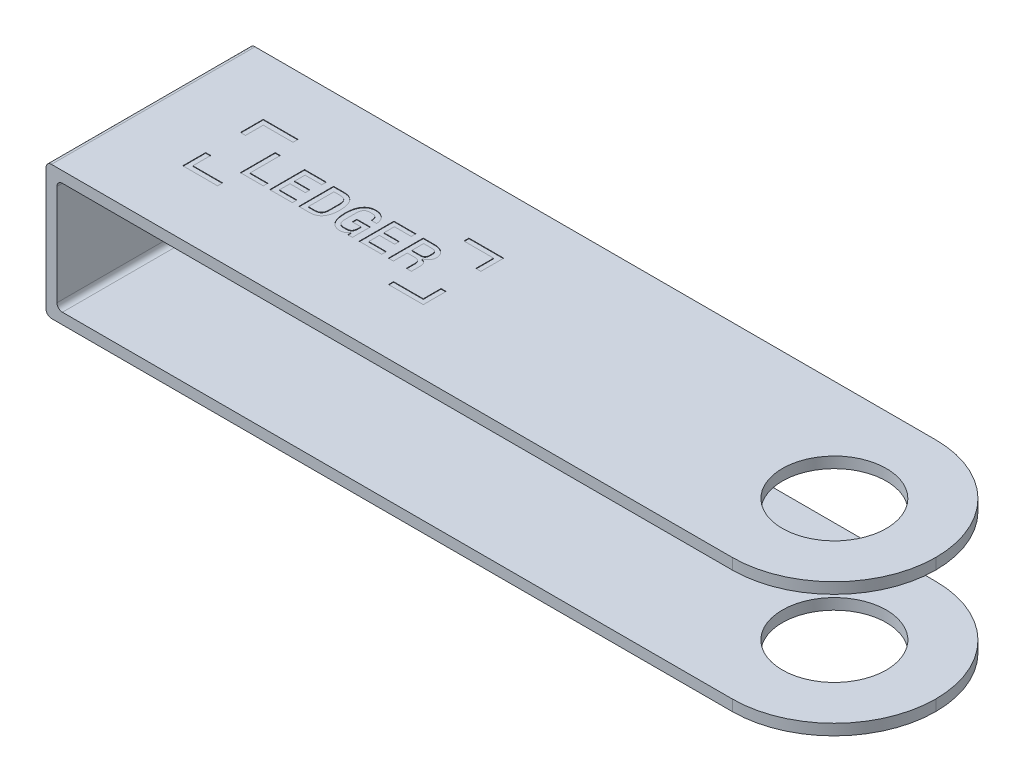
SolidWorks part; units mm, degrees
material "Commercialement pur CP-Ti UNS R50400 (SS)"
ref_plane "Plan de face" through (0, 0, 0) normal (0, 0, 1) x (1, 0, 0)
ref_plane "Plan de dessus" through (0, 0, 0) normal (0, 1, 0) x (1, 0, 0)
ref_plane "Plan de droite" through (0, 0, 0) normal (1, 0, 0) x (0, 0, -1)
sketch "Esquisse1" plane through (0, 0, 0) normal (0, 0, 1) x (1, 0, 0)
  line L0 (0, 0) -> (72, 0) construction
  line L1 (72, 0) -> (72, -1.0004) construction
  line L2 (0.5, 0) -> (72, 0)
  line L3 (0, -0.5) -> (0, -11.7)
  line L4 (0.5, -12.2) -> (72, -12.2)
  line L5 (72, 0) -> (72, -1.0004)
  line L6 (72, -1.0004) -> (0, -1.0004) construction
  line L7 (0, -1.0004) -> (1.001, -1.0004) construction
  line L8 (1.001, -1.0004) -> (1.001, -12.2) construction
  line L9 (1.001, -12.2) -> (1.001, -11.1998) construction
  line L10 (1.001, -11.1998) -> (72, -11.1998) construction
  line L11 (72, -1.0004) -> (1.501, -1.0004)
  line L12 (1.001, -1.5004) -> (1.001, -10.6998)
  line L13 (1.501, -11.1998) -> (72, -11.1998)
  line L14 (72, -11.1998) -> (72, -12.2)
  arc A0 (0, -11.7) -> (0.5, -12.2) centre (0.5, -11.7) ccw
  arc A1 (1.001, -10.6998) -> (1.501, -11.1998) centre (1.501, -10.6998) ccw
  arc A2 (1.501, -1.0004) -> (1.001, -1.5004) centre (1.501, -1.5004) ccw
  arc A3 (0, -0.5) -> (0.5, 0) centre (0.5, -0.5) cw
  dimension "D3" = 0.5
  dimension "D1" = 72
  dimension "D2" = 12.2
extrude "Boss.-Extru.1" add sketch "Esquisse1" along normal blind 18.6
fillet "Congé1" radius 9.3 4 edges at (72, -11.6999, 18.6) (72, -11.6999, 0) (72, -0.5002, 0) (72, -0.5002, 18.6)
sketch "Esquisse2" plane through (0, 0, 0) normal (0, 1, 0) x (1, 0, 0)
  line L0 (62.7, 0) -> (62.7, -18.5429) construction
  circle A0 centre (62.7, -9.2715) radius 4.75
extrude "Enlèv. mat.-Extru.1" cut sketch "Esquisse2" against normal blind 18.6
sketch "Esquisse3" plane through (-8.0039, 0, -2.3563) normal (0, 1, 0) x (1, 0, 0)
  line L0 (33.4116, -14.6086) -> (33.4116, -15.0699)
  line L1 (33.4116, -15.0699) -> (36.589, -15.0699)
  line L2 (36.589, -15.0699) -> (36.589, -12.9832)
  line L3 (36.589, -12.9832) -> (36.1246, -12.9832)
  line L4 (36.1246, -12.9832) -> (36.1246, -14.6086)
  line L5 (36.1246, -14.6086) -> (33.4116, -14.6086)
  line L6 (33.4116, -7.719) -> (33.4116, -8.1804)
  line L7 (33.4116, -8.1804) -> (36.1246, -8.1804)
  line L8 (36.1246, -8.1804) -> (36.1246, -9.8058)
  line L9 (36.1246, -9.8058) -> (36.5859, -9.8058)
  line L10 (36.5859, -9.8058) -> (36.5859, -7.719)
  line L11 (36.5859, -7.719) -> (33.4116, -7.719)
  line L12 (31.774, -11.2998) -> (31.774, -10.2243)
  line L13 (31.774, -10.2243) -> (32.5011, -10.2243)
  line L14 (32.9808, -10.6643) -> (32.9808, -10.8537)
  line L15 (32.5011, -11.2967) -> (31.774, -11.2998)
  line L16 (32.3392, -9.8058) -> (31.3188, -9.8058)
  line L17 (31.3188, -9.8058) -> (31.3188, -12.9832)
  line L18 (31.3188, -12.9832) -> (31.774, -12.9832)
  line L19 (31.774, -12.9832) -> (31.774, -11.7153)
  line L20 (31.774, -11.7153) -> (32.4553, -11.7153)
  line L21 (32.9441, -12.2224) -> (32.9441, -12.9801)
  line L22 (32.9441, -12.9801) -> (33.4085, -12.9801)
  line L23 (33.4085, -12.9801) -> (33.4085, -12.2958)
  line L24 (32.9289, -11.5503) -> (32.9258, -11.4892)
  line L25 (29.1037, -11.5961) -> (30.503, -11.5961)
  line L26 (30.503, -11.5961) -> (30.503, -11.1775)
  line L27 (30.503, -11.1775) -> (29.1037, -11.1775)
  line L28 (29.1037, -11.1775) -> (29.1037, -10.2243)
  line L29 (29.1037, -10.2243) -> (30.6375, -10.2243)
  line L30 (30.6375, -10.2243) -> (30.6375, -9.8058)
  line L31 (30.6375, -9.8058) -> (28.6424, -9.8058)
  line L32 (28.6424, -9.8058) -> (28.6424, -12.9832)
  line L33 (28.6424, -12.9832) -> (30.7077, -12.9832)
  line L34 (30.7077, -12.9832) -> (30.7077, -12.5646)
  line L35 (30.7077, -12.5646) -> (29.1037, -12.5646)
  line L36 (29.1037, -12.5646) -> (29.1037, -11.5961)
  line L37 (27.5853, -11.7611) -> (27.5853, -11.978)
  line L38 (26.9956, -12.586) -> (26.8948, -12.586)
  line L39 (26.2685, -11.8191) -> (26.2685, -10.9667)
  line L40 (26.904, -10.1999) -> (26.9956, -10.1999)
  line L41 (27.5456, -10.7804) -> (28.0436, -10.7804)
  line L42 (27.5425, -12.6838) -> (27.6067, -12.6838)
  line L43 (27.6067, -12.6838) -> (27.6067, -12.9862)
  line L44 (27.6067, -12.9862) -> (28.0252, -12.9862)
  line L45 (28.0252, -12.9862) -> (28.0252, -11.3486)
  line L46 (28.0252, -11.3486) -> (26.794, -11.3486)
  line L47 (26.794, -11.3486) -> (26.794, -11.7641)
  line L48 (26.794, -11.7641) -> (27.5853, -11.7641)
  line L49 (27.5853, -11.7641) -> (27.5853, -11.7611)
  line L50 (23.583, -10.2243) -> (24.0779, -10.2243)
  line L51 (24.7989, -10.9759) -> (24.7989, -11.81)
  line L52 (24.0779, -12.5646) -> (23.583, -12.5646)
  line L53 (23.583, -12.5646) -> (23.583, -10.2243)
  line L54 (24.1085, -9.8058) -> (23.1277, -9.8058)
  line L55 (23.1277, -9.8058) -> (23.1277, -12.9832)
  line L56 (23.1277, -12.9832) -> (24.1176, -12.9832)
  line L57 (20.9372, -11.5961) -> (22.3364, -11.5961)
  line L58 (22.3364, -11.5961) -> (22.3364, -11.1775)
  line L59 (22.3364, -11.1775) -> (20.9372, -11.1775)
  line L60 (20.9372, -11.1775) -> (20.9372, -10.2243)
  line L61 (20.9372, -10.2243) -> (22.4709, -10.2243)
  line L62 (22.4709, -10.2243) -> (22.4709, -9.8058)
  line L63 (22.4709, -9.8058) -> (20.4728, -9.8058)
  line L64 (20.4728, -9.8058) -> (20.4728, -12.9832)
  line L65 (20.4728, -12.9832) -> (22.5381, -12.9832)
  line L66 (22.5381, -12.9832) -> (22.5381, -12.5646)
  line L67 (22.5381, -12.5646) -> (20.9372, -12.5646)
  line L68 (20.9372, -12.5646) -> (20.9372, -11.5961)
  line L69 (18.2577, -9.8058) -> (17.7933, -9.8058)
  line L70 (17.7933, -9.8058) -> (17.7933, -12.9832)
  line L71 (17.7933, -12.9832) -> (19.88, -12.9832)
  line L72 (19.88, -12.9832) -> (19.88, -12.5646)
  line L73 (19.88, -12.5646) -> (18.2577, -12.5646)
  line L74 (18.2577, -12.5646) -> (18.2577, -9.8058)
  line L75 (14.6159, -12.9832) -> (14.6159, -15.0699)
  line L76 (14.6159, -15.0699) -> (17.7933, -15.0699)
  line L77 (17.7933, -15.0699) -> (17.7933, -14.6055)
  line L78 (17.7933, -14.6055) -> (15.0773, -14.6055)
  line L79 (15.0773, -14.6055) -> (15.0773, -12.9801)
  line L80 (15.0773, -12.9801) -> (14.6159, -12.9801)
  line L81 (14.6159, -12.9801) -> (14.6159, -12.9832)
  line L82 (14.6159, -7.719) -> (14.6159, -9.8058)
  line L83 (14.6159, -9.8058) -> (15.0773, -9.8058)
  line L84 (15.0773, -9.8058) -> (15.0773, -8.1804)
  line L85 (15.0773, -8.1804) -> (17.7903, -8.1804)
  line L86 (17.7903, -8.1804) -> (17.7903, -7.719)
  line L87 (17.7903, -7.719) -> (14.6159, -7.719)
  spline S0 degree 3 poles (32.5011, -10.2243) (32.8555, -10.2243) (32.9808, -10.3435) (32.9808, -10.6643) knots 0 0 0 0 1 1 1 1
  spline S1 degree 3 poles (32.9808, -10.8537) (32.9808, -11.1837) (32.8586, -11.2967) (32.5011, -11.2967) knots 0 0 0 0 1 1 1 1
  spline S2 degree 3 poles (32.9258, -11.4892) (33.2558, -11.4036) (33.488, -11.0951) (33.488, -10.7254) knots 0 0 0 0 1 1 1 1
  spline S3 degree 3 poles (33.488, -10.7254) (33.488, -10.4962) (33.3933, -10.2732) (33.2252, -10.1174) knots 0 0 0 0 1 1 1 1
  spline S4 degree 3 poles (33.2252, -10.1174) (33.0083, -9.9096) (32.7181, -9.8058) (32.3392, -9.8058) knots 0 0 0 0 1 1 1 1
  spline S5 degree 3 poles (32.4553, -11.7153) (32.8036, -11.7153) (32.9441, -11.8619) (32.9441, -12.2224) knots 0 0 0 0 1 1 1 1
  spline S6 degree 3 poles (33.4085, -12.2958) (33.4085, -11.7978) (33.2894, -11.6053) (32.9289, -11.5503) knots 0 0 0 0 1 1 1 1
  spline S7 degree 3 poles (27.5853, -11.978) (27.5853, -12.4363) (27.4173, -12.586) (26.9956, -12.586) knots 0 0 0 0 1 1 1 1
  spline S8 degree 3 poles (26.8948, -12.586) (26.4732, -12.586) (26.2685, -12.4485) (26.2685, -11.8191) knots 0 0 0 0 1 1 1 1
  spline S9 degree 3 poles (26.2685, -10.9667) (26.2685, -10.3313) (26.4824, -10.1999) (26.904, -10.1999) knots 0 0 0 0 1 1 1 1
  spline S10 degree 3 poles (26.9956, -10.1999) (27.4081, -10.1999) (27.5395, -10.3526) (27.5456, -10.7804) knots 0 0 0 0 1 1 1 1
  spline S11 degree 3 poles (28.0436, -10.7804) (27.9977, -10.1541) (27.5822, -9.7599) (26.9559, -9.7599) knots 0 0 0 0 1 1 1 1
  spline S12 degree 3 poles (26.9559, -9.7599) (26.6504, -9.7599) (26.3968, -9.8546) (26.2074, -10.038) knots 0 0 0 0 1 1 1 1
  spline S13 degree 3 poles (26.2074, -10.038) (25.9202, -10.3068) (25.7644, -10.759) (25.7644, -11.3945) knots 0 0 0 0 1 1 1 1
  spline S14 degree 3 poles (25.7644, -11.3945) (25.7644, -12.0055) (25.9019, -12.4607) (26.183, -12.7418) knots 0 0 0 0 1 1 1 1
  spline S15 degree 3 poles (26.183, -12.7418) (26.3754, -12.9251) (26.629, -13.029) (26.8948, -13.029) knots 0 0 0 0 1 1 1 1
  spline S16 degree 3 poles (26.8948, -13.029) (27.1667, -13.029) (27.4173, -12.919) (27.5425, -12.6838) knots 0 0 0 0 1 1 1 1
  spline S17 degree 3 poles (24.0779, -10.2243) (24.5454, -10.2243) (24.7989, -10.3435) (24.7989, -10.9759) knots 0 0 0 0 1 1 1 1
  spline S18 degree 3 poles (24.7989, -11.81) (24.7989, -12.4455) (24.5454, -12.5646) (24.0779, -12.5646) knots 0 0 0 0 1 1 1 1
  spline S19 degree 3 poles (24.1176, -12.9832) (24.9853, -12.9832) (25.3061, -12.3263) (25.3061, -11.3945) knots 0 0 0 0 1 1 1 1
  spline S20 degree 3 poles (25.3061, -11.3945) (25.3061, -10.4504) (24.9609, -9.8058) (24.1085, -9.8058) knots 0 0 0 0 1 1 1 1
extrude "Enlèv. mat.-Extru.2" cut sketch "Esquisse3" against normal blind 0.05 contours L86 L87 L82 L83 L84 L85 | L80 L81 L75 L76 L77 L78 L79 | L73 L74 L69 L70 L71 L72 | L67 L68 L57 L58 L59 L60 L61 L62 L63 L64 L65 L66 | S19 S20 L54 L55 L56 L51 S18 L52 L53 L50 S17 | S15 S16 L42 L43 L44 L45 L46 L47 L48 L37 S7 L38 S8 L39 S9 L40 S10 L41 S11 S12 S13 S14 | L35 L36 L25 L26 L27 L28 L29 L30 L31 L32 L33 L34 | L23 S6 L24 S2 S3 S4 L16 L17 L18 L19 L20 S5 L21 L22 L14 S1 L15 L12 L13 S0 | L10 L11 L6 L7 L8 L9 | L4 L5 L0 L1 L2 L3 region at (26.7642, 0, 12.2903) region at (26.9949, 0, 5.4008) region at (24.7985, 0, 7.5542) region at (21.4275, 0, 9.0489) region at (18.9259, 0, 9.1179) region at (17.0272, 0, 7.9671) region at (13.2581, 0, 9.0484) region at (10.2159, 0, 8.8289) region at (6.6501, 0, 10.6254) region at (8.1992, 0, 5.4008)
ref_plane "Plan1" through (0, -6.1, 0) normal (0, 1, 0) x (1, 0, 0)
ref_plane "Plan2" through (0, 0, 9.3) normal (0, 0, 1) x (1, 0, 0)
